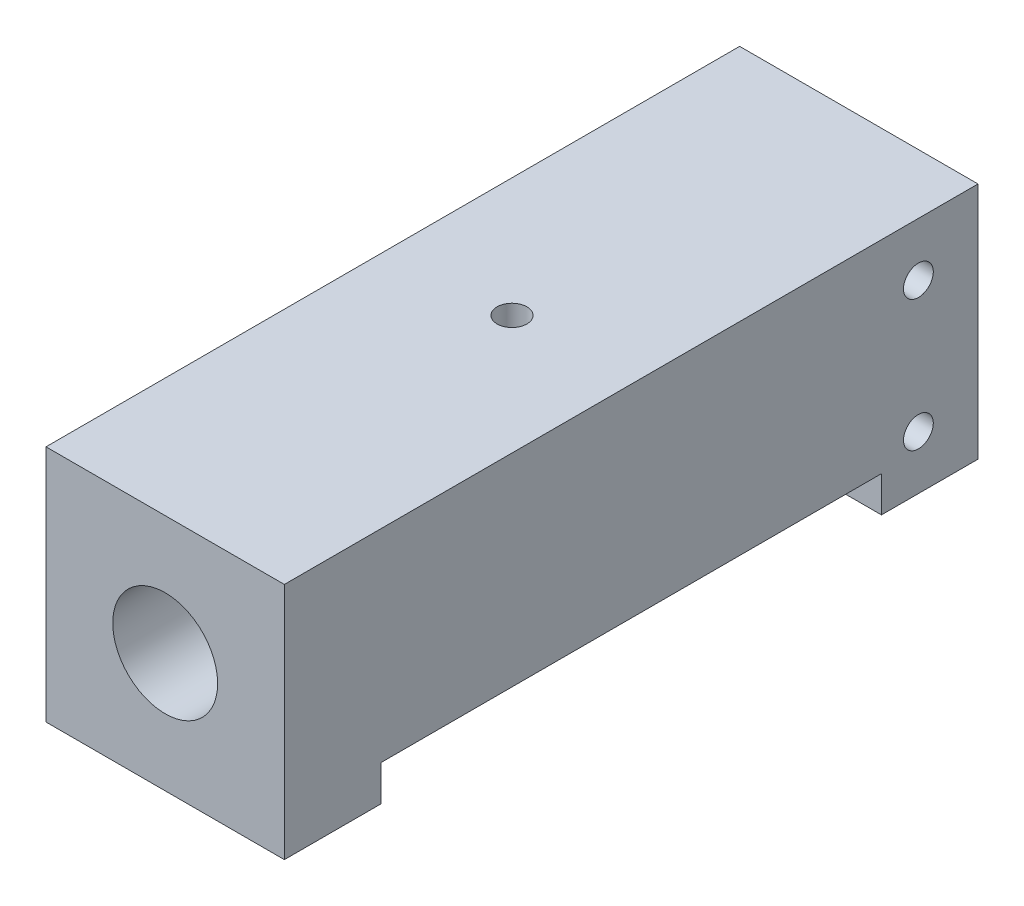
SolidWorks part; units mm, degrees
material "6063-T5"
ref_plane "Piano frontale" through (0, 0, 0) normal (0, 0, 1) x (1, 0, 0)
ref_plane "Piano superiore" through (0, 0, 0) normal (0, 1, 0) x (1, 0, 0)
ref_plane "Piano destro" through (0, 0, 0) normal (1, 0, 0) x (0, 0, -1)
sketch "Schizzo1" plane through (0, 0, 0) normal (0, 0, 1) x (1, 0, 0)
  line L1 (10, -10) -> (-10, -10)
  line L2 (10, -10) -> (10, 10)
  line L3 (10, 10) -> (-10, 10)
  line L4 (-10, -10) -> (-10, 10)
  line L5 (10, -10) -> (-10, 10) construction
  line L6 (10, 10) -> (-10, -10) construction
  point P0 (0, 0)
  dimension "D1" = 20
  dimension "D2" = 20
extrude "Estrusione-Estrusione1" add sketch "Schizzo1" against normal blind 58.2
sketch "Schizzo2" plane through (0, 0, -58.2) normal (0, 0, -1) x (-1, 0, 0)
  circle A0 centre (0, 0) radius 2.05
  dimension "D1" = 4.1
extrude "Taglio-Estrusione1" cut sketch "Schizzo2" against normal through all
sketch "Schizzo3" plane through (0, 0, -58.2) normal (0, 0, -1) x (-1, 0, 0)
  point P0 (0, 0)
hole_wizard "Foro filettato G1/8-1" positions "Schizzo8" profile "Schizzo7" tap size "G1/8" standard "BSI"
sketch "Schizzo8" plane through (0, 0, 0) normal (0, 0, 1) x (1, 0, 0)
  point P0 (0, 0)
sketch "Schizzo7" plane through (0, 0, 0) normal (1, 0, 0) x (0, -1, 0)
  line L0 (0, 0) -> (0, 12.6438)
  line L1 (0, 12.6438) -> (4.4, 10)
  line L2 (4.4, 10) -> (4.4, 0)
  line L5 (4.4, 0) -> (0, 0)
  line L10 (0, 12.6438) -> (-4.4, 10) construction
  line L11 (0, -6.35) -> (0, 107.95) construction
  dimension "Tap Drill Dia." = 8.8
  dimension "Tap Drill Depth" = 10
  dimension "Drill Angle" = 118
sketch "Schizzo11" plane through (0, 10, 0) normal (0, 1, 0) x (1, 0, 0)
  line L0 (0, 58.2) -> (0, 0) construction
  line L1 (10, 58.2) -> (-10, 58.2) construction
  line L2 (10, 29.1) -> (-10, 29.1) construction
  line L3 (10, 58.2) -> (10, 0) construction
  point P10 (0, 29.1)
  point P11 (0, 29.1)
  point P12 (0, 29.1)
hole_wizard "M3 Tapped Hole2" positions "Schizzo3D1" profile "Schizzo12" tap size "M3" standard "DIN"
sketch3d "Schizzo3D1"
  point P0 (0, 10, -29.1)
sketch "Schizzo12" plane through (0, 10, -29.1) normal (1, 0, 0) x (0, 0, 1)
  line L0 (0, 0) -> (0, 5.7511)
  line L1 (0, 5.7511) -> (1.25, 5)
  line L2 (1.25, 5) -> (1.25, 0)
  line L5 (1.25, 0) -> (0, 0)
  line L10 (0, 5.7511) -> (-1.25, 5) construction
  line L11 (0, -6.35) -> (0, 107.95) construction
  dimension "Tap Drill Dia." = 2.5
  dimension "Tap Drill Depth" = 5
  dimension "Drill Angle" = 118
cosmetic thread "Hole Thread4" parameters "D1"=5, "D2"=3
hole_wizard "Foro Ø16.0 (16)-1" positions "Schizzo3D3" profile "Schizzo14" hole size "Ø16.0" standard "ISO"
sketch3d "Schizzo3D3"
  point P0 (0, 0, 0)
  point P3 (0, 0, -58.2)
sketch "Schizzo14" plane through (0, 0, -58.2) normal (1, 0, 0) x (0, 1, 0)
  line L0 (0, 0) -> (0, 16.8069)
  line L1 (0, 16.8069) -> (8, 12)
  line L2 (8, 12) -> (8, 0)
  line L5 (8, 0) -> (0, 0)
  line L10 (0, 16.8069) -> (-8, 12) construction
  line L11 (0, -6.35) -> (0, 107.95) construction
  dimension "Hole Dia." = 16
  dimension "Hole Depth" = 12
  dimension "Drill Angle" = 118
sketch "Schizzo15" plane through (10, 0, 0) normal (1, 0, 0) x (0, 0, -1)
  line L0 (46.2, 0) -> (58.2, 0) construction
  line L1 (46.2, 8) -> (46.2, -8) construction
  line L4 (58.2, -10) -> (58.2, 10) construction
  line L6 (58.2, -10) -> (0, -10) construction
  point P5 (53.2, -5.5)
  point P8 (53.2, 5.5)
  dimension "D1" = 5.5
  dimension "D2" = 7
  dimension "D3" = 5
  dimension "D4" = 4.5
hole_wizard "M3 Tapped Hole3" positions "Schizzo3D4" profile "Schizzo16" tap size "M3" standard "ISO" end condition through all
sketch3d "Schizzo3D4"
  point P0 (10, 5.5, -53.2)
  point P3 (10, -5.5, -53.2)
sketch "Schizzo16" plane through (10, 5.5, -53.2) normal (0, 1, 0) x (0, 0, -1)
  line L0 (0, 0) -> (0, 20)
  line L1 (0, 20) -> (1.25, 20)
  line L2 (1.25, 20) -> (1.25, 0)
  line L5 (1.25, 0) -> (0, 0)
  line L11 (0, -6.35) -> (0, 107.95) construction
  dimension "Thread Major Dia." = 2.5
  dimension "Thru Tap Drill Depth" = 20
sketch "Sketch1" plane through (-10, 0, 0) normal (-1, 0, 0) x (0, 0, 1)
  line L0 (-58.2, 10) -> (-58.2, -10) construction
  line L1 (-58.2, 3) -> (-22, 3)
  line L2 (-58.2, 3) -> (-58.2, -3)
  line L3 (-58.2, -3) -> (-22, -3)
  line L4 (-22, 3) -> (-22, -3)
  line L5 (0, 10) -> (0, -10) construction
  line L6 (0, 0) -> (-22, 0) construction
  point P8 (-22, 0)
  dimension "D1" = 6
  dimension "D2" = 22
extrude "Boss-Extrude1" add sketch "Sketch1" along normal blind 4.9
sketch "Sketch2" plane through (10, 0, 0) normal (1, 0, 0) x (0, 0, -1)
  line L0 (58.2, -10) -> (0, -10) construction
  line L1 (50.1, -10) -> (34.1, -10)
  line L2 (50.1, -10) -> (50.1, -7)
  line L3 (50.1, -7) -> (34.1, -7)
  line L4 (34.1, -7) -> (8.1, -7)
  line L5 (42.1, -7) -> (42.1, -12.5) construction
  line L6 (8.1, -7) -> (8.1, -10)
  line L7 (8.1, -10) -> (34.1, -10)
  line L8 (0, -10) -> (8.1, -10) construction
  line L9 (50.1, -10) -> (58.2, -10) construction
  dimension "D1" = 16
  dimension "D2" = 3
extrude "Cut-Extrude1" cut sketch "Sketch2" against normal through all
sketch "Sketch3" plane through (0, 0, -22) normal (0, 0, 1) x (1, 0, 0)
  point P0 (-13, 0)
hole_wizard "M3 Tapped Hole4" positions "Sketch6" profile "Sketch7" tap size "M3" standard "ISO"
sketch "Sketch6" plane through (0, 0, -22) normal (0, 0, 1) x (1, 0, 0)
  point P0 (-13, 0)
sketch "Sketch7" plane through (-13, 0, -22) normal (1, 0, 0) x (0, -1, 0)
  line L0 (0, 0) -> (0, 20.7511)
  line L1 (0, 20.7511) -> (1.25, 20)
  line L2 (1.25, 20) -> (1.25, 0)
  line L5 (1.25, 0) -> (0, 0)
  line L10 (0, 20.7511) -> (-1.25, 20) construction
  line L11 (0, -6.35) -> (0, 107.95) construction
  dimension "Tap Drill Dia." = 2.5
  dimension "Tap Drill Depth" = 20
  dimension "Drill Angle" = 118
